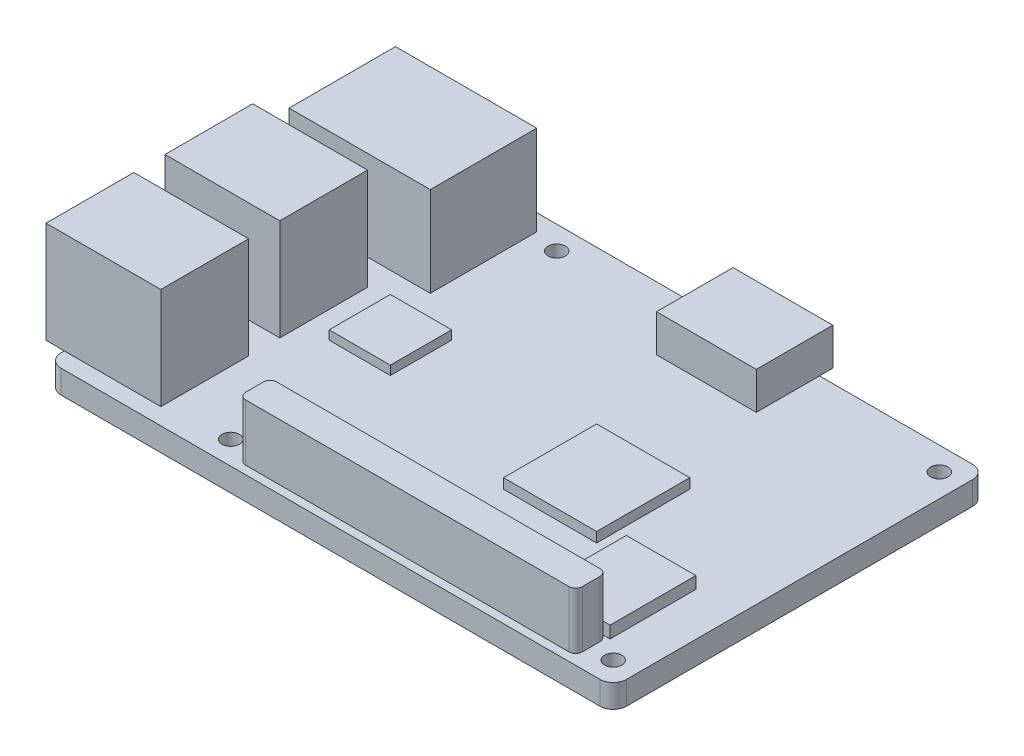
SolidWorks part; units mm, degrees
ref_plane "Front Plane" through (0, 0, 0) normal (0, 0, 1) x (1, 0, 0)
ref_plane "Top Plane" through (0, 0, 0) normal (0, 1, 0) x (1, 0, 0)
ref_plane "Right Plane" through (0, 0, 0) normal (1, 0, 0) x (0, 0, -1)
sketch "Sketch1" plane through (0, 0, 0) normal (0, 1, 0) x (1, 0, 0)
  line L1 (2, 0) -> (83, 0)
  line L2 (0, 2) -> (0, 54)
  line L3 (2, 56) -> (83, 56)
  line L4 (85, 2) -> (85, 54)
  line L5 (-2.76, 33.58) -> (14.5, 33.58)
  line L6 (-2.76, 33.58) -> (-2.76, 20.38)
  line L7 (28.5, 1.25) -> (77.1, 1.25)
  line L8 (27.5, 2.25) -> (27.5, 4.9184)
  line L9 (28.5, 5.9184) -> (77.1, 5.9184)
  line L10 (78.1, 2.25) -> (78.1, 4.9184)
  line L11 (68.05, 18.9184) -> (78.5, 18.9184)
  line L12 (68.05, 18.9184) -> (68.05, 6.0184)
  line L13 (68.05, 6.0184) -> (78.5, 6.0184)
  line L14 (78.5, 18.9184) -> (78.5, 6.0184)
  line L15 (51, 31.5) -> (65, 31.5)
  line L16 (51, 31.5) -> (51, 17.5)
  line L17 (51, 17.5) -> (65, 17.5)
  line L18 (65, 31.5) -> (65, 17.5)
  line L19 (-1.23, 53.5) -> (20, 53.5)
  line L20 (-1.23, 53.5) -> (-1.23, 37.5)
  line L21 (-1.23, 37.5) -> (20, 37.5)
  line L22 (20, 53.5) -> (20, 37.5)
  line L23 (-2.76, 20.38) -> (14.5, 20.38)
  line L24 (14.5, 33.58) -> (14.5, 20.38)
  line L25 (-2.76, 15.7) -> (14.5, 15.7)
  line L26 (-2.76, 15.7) -> (-2.76, 2.5)
  line L27 (-2.76, 2.5) -> (14.5, 2.5)
  line L28 (14.5, 15.7) -> (14.5, 2.5)
  line L29 (18.5, 33) -> (27.7, 33)
  line L30 (18.5, 33) -> (18.5, 23.8)
  line L31 (18.5, 23.8) -> (27.7, 23.8)
  line L32 (27.7, 33) -> (27.7, 23.8)
  line L33 (45, 58) -> (60, 58)
  line L34 (45, 58) -> (45, 46.5)
  line L35 (45, 46.5) -> (60, 46.5)
  line L36 (60, 58) -> (60, 46.5)
  arc A0 (0, 2) -> (2, 0) centre (2, 2) ccw
  arc A1 (83, 0) -> (85, 2) centre (83, 2) ccw
  arc A2 (83, 56) -> (85, 54) centre (83, 54) cw
  arc A3 (0, 54) -> (2, 56) centre (2, 54) cw
  circle A4 centre (81.5, 52.5) radius 1.3
  circle A5 centre (81.5, 3.5) radius 1.3
  circle A6 centre (24, 52.5) radius 1.3
  circle A7 centre (24, 3.5) radius 1.3
  circle A8 centre (24, 52.5) radius 2.95
  circle A9 centre (24, 3.5) radius 2.95
  circle A10 centre (81.5, 52.5) radius 2.95
  circle A11 centre (81.5, 3.5) radius 2.95
  arc A12 (77.1, 1.25) -> (78.1, 2.25) centre (77.1, 2.25) ccw
  arc A13 (78.1, 4.9184) -> (77.1, 5.9184) centre (77.1, 4.9184) ccw
  arc A14 (27.5, 4.9184) -> (28.5, 5.9184) centre (28.5, 4.9184) cw
  arc A15 (27.5, 2.25) -> (28.5, 1.25) centre (28.5, 2.25) ccw
  point P7 (0, 0)
  point P10 (85, 0)
  point P13 (85, 56)
  point P16 (0, 56)
  point P41 (78.1, 5.9184)
  point P44 (27.5, 5.9184)
  dimension "D3" = 2
  dimension "D6" = 2.6
  dimension "D7" = 2.6
  dimension "D10" = 5.9
  dimension "D11" = 5.9
  dimension "D15" = 1
  dimension "D1" = 85
  dimension "D2" = 56
  dimension "D4" = 3.5
  dimension "D5" = 3.5
  dimension "D8" = 24
  dimension "D9" = 3.5
  dimension "D12" = 50.6
  dimension "D13" = 3.5
  dimension "D14" = 1.25
  dimension "D16" = 10.45
  dimension "D17" = 12.9
  dimension "D18" = 6.5
  dimension "D19" = 0.1
  dimension "D20" = 14
  dimension "D21" = 14
  dimension "D22" = 20
  dimension "D23" = 17.5
  dimension "D24" = 21.23
  dimension "D25" = 16
  dimension "D26" = 2.5
  dimension "D27" = 20
  dimension "D28" = 13.2
  dimension "D29" = 17.26
  dimension "D30" = 13.2
  dimension "D31" = 17.26
  dimension "D32" = 2.5
  dimension "D33" = 14.5
  dimension "D34" = 14.5
  dimension "D35" = 4.68
  dimension "D36" = 9.2
  dimension "D37" = 9.2
  dimension "D38" = 23
  dimension "D39" = 4
  dimension "D40" = 15
  dimension "D41" = 11.5
  dimension "D42" = 9.5
  dimension "D43" = 40
extrude "Boss-Extrude1" add sketch "Sketch1" against normal blind 3.5 contours L28 L25 L2 L27 | L24 L5 L2 L23 | L22 L19 L2 L21 | L32 L29 L30 L31 | A8 A6 | L14 L11 L12 L13 | L8 A15 L7 A12 L10 A13 L9 A14 | A9 A7 | A11 A5 | L36 L3 L34 L35 | L18 L15 L16 L17 | A3 L2 L19 L22 L21 L5 L24 L23 L25 L28 L27 A0 L1 A1 L4 A2 L3 L36 L35 L34 A15 L8 A14 L9 A13 L10 A12 L7 A9 A8 L11 L14 L13 L12 L15 L18 L17 L16 L29 L32 L31 | A10 | A4 region at (46.7458, 0, -29.0764) region at (7.25, 0, -9.1) region at (7.25, 0, -26.98) region at (52.5, 0, -51.25) region at (10, 0, -45.5) region at (52.8, 0, -3.5842) region at (73.275, 0, -12.4684) region at (58, 0, -24.5) region at (23.1, 0, -28.4) region at (21.1334, 0, -52.5) region at (21.1334, 0, -3.5) region at (78.6334, 0, -3.5)
extrude "Boss-Extrude2" add sketch "Sketch1<3>" along normal blind 13.5 contours L20 L21 L22 L19
sketch "Sketch1<3>" plane through (0, 0, 0) normal (0, 1, 0) x (1, 0, 0) same geometry as "Sketch1"
extrude "Boss-Extrude3" add sketch "Sketch1<4>" along normal blind 15.25 contours L6 L23 L2 L5 | L24 L5 L2 L23 | L26 L27 L2 L25 | L28 L25 L2 L27 region at (-1.38, 0, -9.1) region at (7.25, 0, -9.1) region at (-1.38, 0, -26.98) region at (7.25, 0, -26.98)
sketch "Sketch1<4>" plane through (0, 0, 0) normal (0, 1, 0) x (1, 0, 0) same geometry as "Sketch1"
extrude "Boss-Extrude4" add sketch "Sketch1<5>" along normal blind 1.5 contours L18 L15 L16 L17 region at (58, 0, -24.5)
sketch "Sketch1<5>" plane through (0, 0, 0) normal (0, 1, 0) x (1, 0, 0) same geometry as "Sketch1"
extrude "Boss-Extrude5" add sketch "Sketch1<6>" along normal blind 5.6 contours L33 L36 L35 L34
sketch "Sketch1<6>" plane through (0, 0, 0) normal (0, 1, 0) x (1, 0, 0) same geometry as "Sketch1"
extrude "Boss-Extrude6" add sketch "Sketch1<7>" along normal blind 1.35 contours L32 L29 L30 L31 region at (23.1, 0, -28.4)
sketch "Sketch1<7>" plane through (0, 0, 0) normal (0, 1, 0) x (1, 0, 0) same geometry as "Sketch1"
extrude "Boss-Extrude7" add sketch "Sketch1<8>" along normal blind 1.8 contours L14 L11 L12 L13 region at (73.275, 0, -12.4684)
sketch "Sketch1<8>" plane through (0, 0, 0) normal (0, 1, 0) x (1, 0, 0) same geometry as "Sketch1"
extrude "Boss-Extrude8" add sketch "Sketch1<9>" along normal blind 8.5 contours L8 A15 L7 A12 L10 A13 L9 A14 region at (52.8, 0, -3.5842)
sketch "Sketch1<9>" plane through (0, 0, 0) normal (0, 1, 0) x (1, 0, 0) same geometry as "Sketch1"
sketch "Sketch3" plane through (-1.23, 0, 0) normal (-1, 0, 0) x (0, 0, 1)
  line L0 (-53.5, 13.5) -> (-37.5, 13.5) construction
  line L1 (-51.4, 10.7) -> (-39.6, 10.7)
  line L2 (-51.4, 10.7) -> (-51.4, 4.03)
  line L3 (-51.4, 4.03) -> (-48.59, 4.03)
  line L4 (-39.6, 10.7) -> (-39.6, 4.03)
  line L5 (-53.5, 13.5) -> (-53.5, 0) construction
  line L6 (-37.5, 13.5) -> (-37.5, 0) construction
  line L7 (-42.41, 4.03) -> (-39.6, 4.03)
  line L9 (-48.59, 4.03) -> (-48.59, 0.23)
  line L10 (-48.59, 0.23) -> (-42.41, 0.23)
  line L11 (-42.41, 4.03) -> (-42.41, 0.23)
  dimension "D1" = 11.8
  dimension "D2" = 6.67
  dimension "D3" = 2.8
  dimension "D4" = 2.1
  dimension "D5" = 2.1
  dimension "D6" = 3.8
  dimension "D7" = 6.18
  dimension "D8" = 4.91
  dimension "D9" = 4.91
extrude "Cut-Extrude1" cut sketch "Sketch3" against normal blind 10
